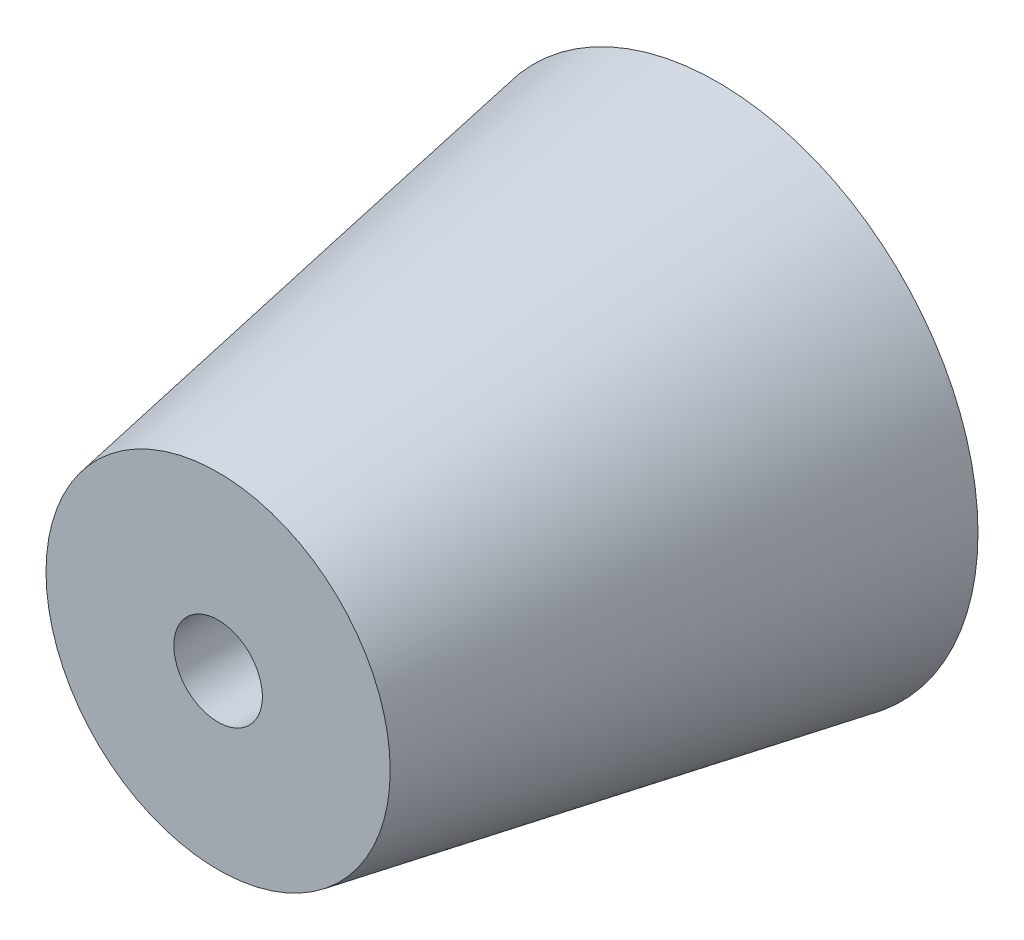
SolidWorks part; units mm, degrees
material "ABS"
ref_plane "Front Plane" through (0, 0, 0) normal (0, 0, 1) x (1, 0, 0)
ref_plane "Top Plane" through (0, 0, 0) normal (0, 1, 0) x (1, 0, 0)
ref_plane "Right Plane" through (0, 0, 0) normal (1, 0, 0) x (0, 0, -1)
sketch "Sketch1" plane through (0, 0, 0) normal (0, 0, 1) x (1, 0, 0)
  circle A0 centre (0, 0) radius 17.5
  dimension "D1" = 35
extrude "Boss-Extrude" add sketch "Sketch1" along normal blind 50.8 and the other way blind 0.01
draft "Draft3" type of draft neutral plane draft angle 10 faces to draft 1 face at (17.5, 0, -0.01) neutral plane through (0, 0, 50.8) neutral plane normal (0, 0, 1) parameters "D1"=10
sketch "Sketch2" plane through (0, 0, -0.01) normal (0, 0, -1) x (-1, 0, 0)
  circle A0 centre (0, 0) radius 4.5
  dimension "D1" = 9
extrude "Cut-Extrude1" cut sketch "Sketch2" against normal through all
sketch "Sketch3" plane through (0, 0, -0.01) normal (0, 0, -1) x (-1, 0, 0)
  circle A0 centre (0, 0) radius 11.5
extrude "Cut-Extrude3" cut sketch "Sketch3" against normal blind 8
